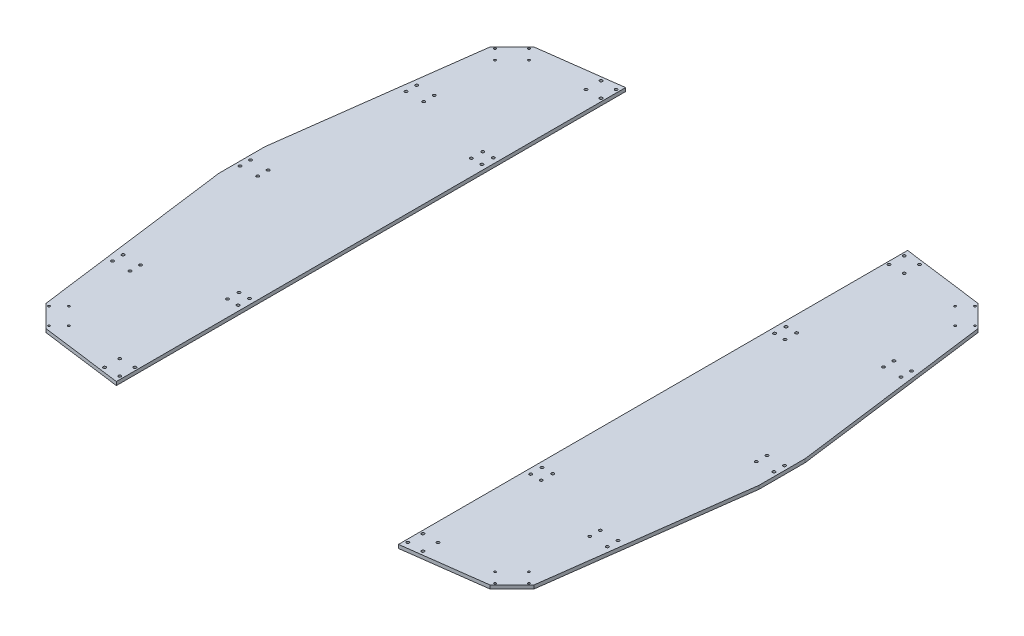
SolidWorks part; units mm, degrees
ref_plane "前视基准面" through (0, 0, 0) normal (0, 0, 1) x (1, 0, 0)
ref_plane "上视基准面" through (0, 0, 0) normal (0, 1, 0) x (1, 0, 0)
ref_plane "右视基准面" through (0, 0, 0) normal (1, 0, 0) x (0, 0, -1)
other "Configuration Table"
sketch "草图1" plane through (0, 0, 0) normal (0, 1, 0) x (1, 0, 0)
  line L0 (-314.9222, 345.9222) -> (-345.9222, 314.9222)
  line L5 (325, -325) -> (-325, 325) construction
  line L6 (325, 325) -> (-325, -325) construction
  line L7 (0, 325) -> (0, -325) construction
  line L8 (-325, 0) -> (325, 0) construction
  line L9 (314.9222, 345.9222) -> (32.7201, 383.0748)
  line L10 (314.9222, 345.9222) -> (345.9222, 314.9222)
  line L11 (-383.07, 11.7425) -> (-230, 11.7425) construction
  line L12 (-314.9222, 345.9222) -> (-32.7201, 383.0748)
  line L13 (0, 325) -> (0, 399.6983)
  line L14 (-32.7201, 383.0748) -> (32.7201, 383.0748)
  line L15 (314.9222, -345.9222) -> (32.7201, -383.0748)
  line L16 (-32.7201, -383.0748) -> (32.7201, -383.0748)
  line L17 (-314.9222, -345.9222) -> (-32.7201, -383.0748)
  line L18 (-314.9222, -345.9222) -> (-345.9222, -314.9222)
  line L19 (-345.9222, 314.9222) -> (-383.0748, 32.7201)
  line L20 (-383.0748, -32.7201) -> (-383.0748, 32.7201)
  line L21 (-345.9222, -314.9222) -> (-383.0748, -32.7201)
  line L22 (-345.9222, -314.9222) -> (-314.9222, -345.9222)
  line L23 (345.9222, -314.9222) -> (314.9222, -345.9222)
  line L24 (345.9222, -314.9222) -> (383.0748, -32.7201)
  line L25 (383.0748, 32.7201) -> (383.0748, -32.7201)
  line L26 (345.9222, 314.9222) -> (383.0748, 32.7201)
  line L27 (-383.07, -14.2575) -> (-230, -14.2575) construction
  line L28 (383.07, -11.0948) -> (230, -11.0948) construction
  line L29 (361.6863, 195.182) -> (230, 195.182) construction
  line L30 (358.2633, 221.182) -> (230, 221.182) construction
  line L31 (-358.2633, 221.182) -> (-230, 221.182) construction
  line L32 (-361.6863, 195.182) -> (-230, 195.182) construction
  line L33 (361.6863, -195.182) -> (230, -195.182) construction
  line L34 (358.2633, -221.182) -> (230, -221.182) construction
  line L35 (-361.6863, -195.182) -> (-230, -195.182) construction
  line L36 (-358.2633, -221.182) -> (-230, -221.182) construction
  line L37 (-228, -357.3657) -> (-228, 357.3618) construction
  line L38 (-202, -360.7887) -> (-202, 360.7847) construction
  circle A5 centre (0, 0) radius 250
  circle A6 centre (302.1379, 326.1795) radius 1.5
  circle A7 centre (316.28, 340.3217) radius 1.5
  circle A8 centre (340.3217, 316.28) radius 1.5
  circle A9 centre (326.1795, 302.1379) radius 1.5
  circle A10 centre (302.1379, -326.1795) radius 1.5
  circle A11 centre (316.28, -340.3217) radius 1.5
  circle A12 centre (326.1795, -302.1379) radius 1.5
  circle A13 centre (340.3217, -316.28) radius 1.5
  circle A14 centre (-326.1795, -302.1379) radius 1.5
  circle A15 centre (-340.3217, -316.28) radius 1.5
  circle A16 centre (-302.1379, -326.1795) radius 1.5
  circle A17 centre (-316.28, -340.3217) radius 1.5
  circle A18 centre (-302.1379, 326.1795) radius 1.5
  circle A19 centre (-316.28, 340.3217) radius 1.5
  circle A20 centre (-326.1795, 302.1379) radius 1.5
  circle A21 centre (-340.3217, 316.28) radius 1.5
  circle A22 centre (350.9184, 215.682) radius 2
  circle A23 centre (377.0748, 9.4052) radius 2
  circle A24 centre (350.9184, 200.682) radius 2
  circle A25 centre (325.9184, 215.682) radius 2
  circle A26 centre (325.9184, 200.682) radius 2
  circle A27 centre (377.0748, -5.5948) radius 2
  circle A28 centre (352.0748, 9.4052) radius 2
  circle A29 centre (352.0748, -5.5948) radius 2
  circle A30 centre (350.9184, -200.682) radius 2
  circle A31 centre (350.9184, -215.682) radius 2
  circle A32 centre (325.9184, -200.682) radius 2
  circle A33 centre (325.9184, -215.682) radius 2
  circle A34 centre (-350.9184, -200.682) radius 2
  circle A35 centre (-325.9184, -200.682) radius 2
  circle A36 centre (-350.9184, -215.682) radius 2
  circle A37 centre (-325.9184, -215.682) radius 2
  circle A38 centre (-377.0748, 6.2425) radius 2
  circle A39 centre (-352.0748, 6.2425) radius 2
  circle A40 centre (-377.0748, -8.7575) radius 2
  circle A41 centre (-352.0748, -8.5322) radius 2
  circle A42 centre (-350.9184, 215.682) radius 2
  circle A43 centre (-350.9184, 200.682) radius 2
  circle A44 centre (-325.9184, 215.682) radius 2
  circle A45 centre (-325.9184, 200.682) radius 2
  circle A46 centre (-222.5, -164.8255) radius 2
  circle A47 centre (-207.5, -164.8255) radius 2
  circle A48 centre (-222.5, -181.0301) radius 2
  circle A49 centre (-207.5, -181.0301) radius 2
  circle A50 centre (-222.5, 181.0301) radius 2
  circle A51 centre (-207.5, 164.8255) radius 2
  circle A52 centre (-222.5, 164.8255) radius 2
  circle A53 centre (-207.5, 181.0301) radius 2
  circle A54 centre (207.5, -164.8255) radius 2
  circle A55 centre (222.5, -164.8255) radius 2
  circle A56 centre (207.5, -181.0301) radius 2
  circle A57 centre (222.5, -181.0301) radius 2
  circle A58 centre (207.5, 164.8255) radius 2
  circle A59 centre (222.5, 164.8255) radius 2
  circle A60 centre (207.5, 181.0301) radius 2
  circle A61 centre (222.5, 181.0301) radius 2
  point P0 (0, 0)
  point P13 (0, 383.0748)
  point P24 (-330.4222, -330.4222)
  point P75 (0, 0)
  dimension "D6" = 25
  dimension "D7" = 15
  dimension "D8" = 500
  dimension "D5" = 4
  dimension "D13" = 6
  dimension "D14" = 6
  dimension "D15" = 6
  dimension "D16" = 6
  dimension "D17" = 25
  dimension "D20" = 8
  dimension "D21" = 25
  dimension "D23" = 8
  dimension "D28" = 5.5
  dimension "D29" = 5.5
  dimension "D30" = 5.5
  dimension "D31" = 5.5
  dimension "D32" = 5.5
  dimension "D33" = 5.5
  dimension "D35" = 5.5
  dimension "D1" = 650
  dimension "D2" = 650
  dimension "D3" = 31
  dimension "D4" = 142.5
  dimension "D9" = 5.5
  dimension "D10" = 5.5
  dimension "D11" = 25
  dimension "D12" = 25
  dimension "D18" = 15
  dimension "D19" = 5.5
  dimension "D22" = 25
  dimension "D24" = 25
  dimension "D25" = 25
  dimension "D26" = 25
  dimension "D27" = 5.5
  dimension "D34" = 5.5
  dimension "D36" = 5.5
extrude "凸台-拉伸2" add sketch "草图1" along normal blind 5 contours L26 L10 L9 L14 L12 L0 L19 L20 L21 L18 L17 L16 L15 L23 L24 L25 | A13 L22 | L22 | A13 L18 region at (-172.4069, 0, -353.7562)
sketch "草图2" plane through (0, 5, 0) normal (0, 1, 0) x (1, 0, 0)
  line L0 (0, 0) -> (-330.4222, -330.4222) construction
  line L1 (0, 383.0748) -> (0, -383.0748)
  line L2 (-32.7201, 383.0748) -> (32.7201, 383.0748) construction
  line L3 (-32.7201, -383.0748) -> (32.7201, -383.0748) construction
  line L4 (-200, 361.052) -> (-200, -361.052)
  line L5 (-314.9222, 345.9222) -> (-32.7201, 383.0748) construction
  line L6 (-314.9222, -345.9222) -> (-32.7201, -383.0748) construction
  line L7 (200, 361.052) -> (200, -361.052)
  line L8 (314.9222, 345.9222) -> (32.7201, 383.0748) construction
  line L9 (314.9222, -345.9222) -> (32.7201, -383.0748) construction
  line L10 (-200, 361.052) -> (-200, 484.7149)
  line L11 (-200, 484.7149) -> (200, 484.7149)
  line L12 (200, 484.7149) -> (200, 361.052)
  line L13 (-200, -361.052) -> (-200, -418.819)
  line L14 (-200, -418.819) -> (200, -418.819)
  line L15 (200, -418.819) -> (200, -361.052)
  dimension "D1" = 200
  dimension "D2" = 200
extrude "切除-拉伸1" cut sketch "草图2" against normal blind 122 and the other way through all contours L4 L1 | L7 L1 | L7 L1 | L4 L1 | L0 L4 region at (-190.1188, 5, -422.8834)
sketch "草图3" plane through (0, 0, 0) normal (0, -1, 0) x (-1, 0, 0)
  circle A0 centre (225.7527, -352.0225) radius 2
  circle A1 centre (204.2473, -352.0225) radius 2
  circle A2 centre (225.7527, -330.517) radius 2
  circle A3 centre (204.2473, -330.517) radius 2
extrude "切除-拉伸2" cut sketch "草图3" along normal through all and the other way blind 39 contours A0 | A1 | A2 | A3
sketch "草图4" plane through (0, 5, 0) normal (0, 1, 0) x (1, 0, 0)
  line L0 (-225.7527, 352.0186) -> (-204.2473, 352.0186)
  line L1 (-215, 352.0186) -> (-215, 326.2032)
  circle A0 centre (-225.7527, 352.0186) radius 2
  circle A1 centre (-204.2473, 352.0186) radius 2
  circle A2 centre (-225.7527, 330.5131) radius 2
  circle A3 centre (-204.2473, 330.5131) radius 2
  circle A4 centre (204.2473, 330.5131) radius 2
  circle A5 centre (225.7527, 330.5131) radius 2
  circle A6 centre (204.2473, 352.0186) radius 2
  circle A7 centre (225.7527, 352.0186) radius 2
  circle A8 centre (204.2473, -352.0225) radius 2
  circle A9 centre (225.7527, -352.0225) radius 2
  circle A10 centre (204.2473, -330.517) radius 2
  circle A11 centre (225.7527, -330.517) radius 2
  dimension "D1" = 4
extrude "切除-拉伸3" cut sketch "草图4" against normal through all and the other way blind 20 contours A8 | A9 | A11 | A4 | A6 | A5 | A7 | A1 | A0 | A2 | A3 | A10 region at (-204.2473, 5, -353.962) region at (-227.6962, 5, -352.0186) region at (-225.7527, 5, -330.5131) region at (-204.2473, 5, -330.5131) region at (204.2473, 5, -330.5131) region at (225.7527, 5, -330.5131) region at (204.2473, 5, -352.0186) region at (225.7527, 5, -352.0186) region at (204.2473, 5, 352.0225) region at (225.7527, 5, 352.0225) region at (225.7527, 5, 330.517)
sketch "草图5" plane through (0, 5, 0) normal (0, 1, 0) x (1, 0, 0)
  line L0 (-200, 150) -> (-200, -150)
  line L1 (200, 150) -> (200, -150)
  circle A0 centre (0, 0) radius 250
  arc M39 (-200, -150) -> (-200, 150) centre (0, 0) cw
extrude "凸台-拉伸3" add sketch "草图5" against normal blind 5 contours L0 M39 | L1 A0 region at (-220.182, 5, 0) region at (220.182, 5, 0)
